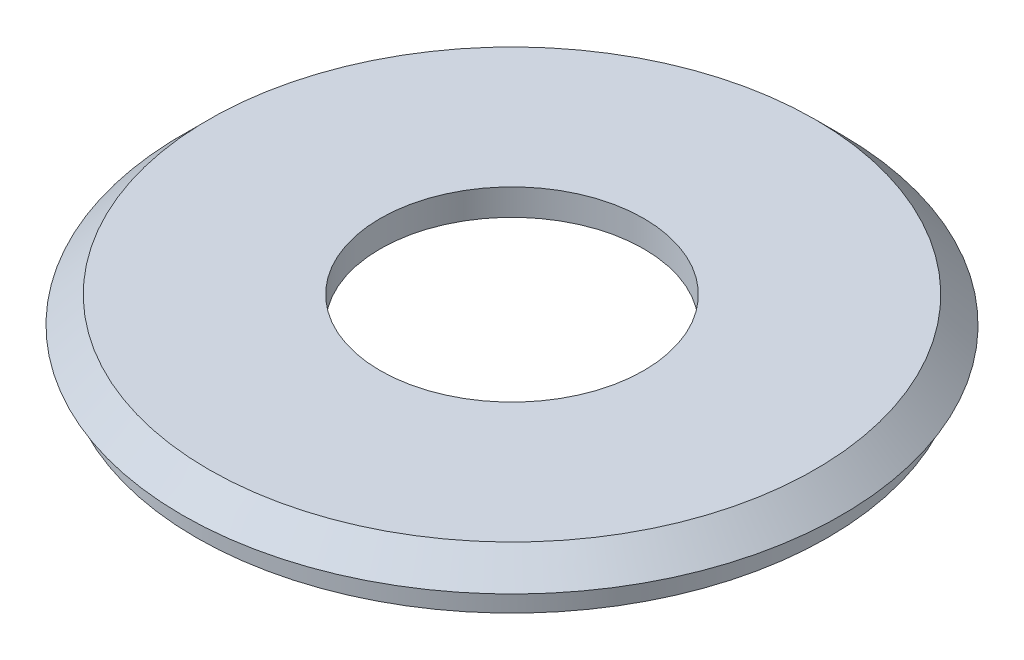
SolidWorks part; units mm, degrees
ref_plane "Front Plane" through (0, 0, 0) normal (0, 0, 1) x (1, 0, 0)
ref_plane "Top Plane" through (0, 0, 0) normal (0, 1, 0) x (1, 0, 0)
ref_plane "Right Plane" through (0, 0, 0) normal (1, 0, 0) x (0, 0, -1)
sketch "Sketch1" plane through (0, 0, 0) normal (0, 1, 0) x (1, 0, 0)
  circle A0 centre (0, 0) radius 125
  dimension "D1" = 250
extrude "Boss-Extrude1" add sketch "Sketch1" along normal blind 10
chamfer "Chamfer1" distance 10 angle 45 1 edges at (0, 10, 125)
sketch "Sketch2" plane through (0, 0, 0) normal (0, -1, 0) x (1, 0, 0)
  circle A0 centre (0, 0) radius 119.75
  circle A1 centre (0, 0) radius 115
  dimension "D1" = 239.5
  dimension "D2" = 230
extrude "Boss-Extrude2" add sketch "Sketch2" along normal blind 10
sketch "Sketch3" plane through (0, 10, 0) normal (0, 1, 0) x (1, 0, 0)
  circle A0 centre (0, 0) radius 50
  dimension "D1" = 100
extrude "Cut-Extrude1" cut sketch "Sketch3" against normal blind 20
